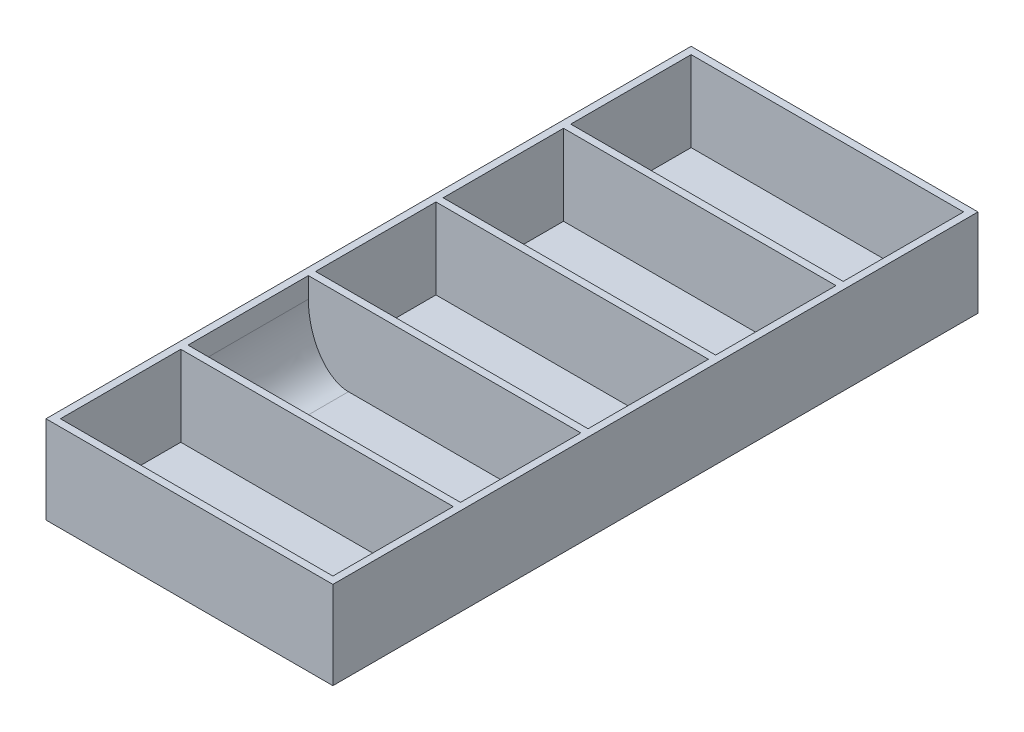
SolidWorks part; units mm, degrees
note: The reader was unsure of these and kept them because the rebuilt part matched: shared geometry of "Sketch1<6>".
ref_plane "Front Plane" through (0, 0, 0) normal (0, 0, 1) x (1, 0, 0)
ref_plane "Top Plane" through (0, 0, 0) normal (0, 1, 0) x (1, 0, 0)
ref_plane "Right Plane" through (0, 0, 0) normal (1, 0, 0) x (0, 0, -1)
sketch "Sketch1" plane through (0, 0, 0) normal (0, 1, 0) x (1, 0, 0)
  line L53 (0, 0) -> (71.6, 0)
  line L54 (0, 0) -> (0, 161)
  line L55 (0, 161) -> (71.6, 161)
  line L56 (71.6, 0) -> (71.6, 161)
  line L57 (1.8, 31.84) -> (69.8, 31.84)
  line L58 (1.8, 31.84) -> (1.8, 1.8)
  line L59 (1.8, 1.8) -> (69.8, 1.8)
  line L60 (69.8, 31.84) -> (69.8, 1.8)
  line L61 (1.8, 95.52) -> (69.8, 95.52)
  line L62 (1.8, 95.52) -> (1.8, 65.48)
  line L63 (1.8, 65.48) -> (69.8, 65.48)
  line L64 (69.8, 95.52) -> (69.8, 65.48)
  line L65 (69.8, 63.68) -> (1.8, 63.68)
  line L66 (69.8, 63.68) -> (69.8, 33.64)
  line L67 (69.8, 33.64) -> (1.8, 33.64)
  line L68 (1.8, 63.68) -> (1.8, 33.64)
  line L69 (69.8, 97.32) -> (1.8, 97.32)
  line L70 (69.8, 97.32) -> (69.8, 127.36)
  line L71 (69.8, 127.36) -> (1.8, 127.36)
  line L72 (1.8, 97.32) -> (1.8, 127.36)
  line L73 (69.8, 129.16) -> (1.8, 129.16)
  line L74 (69.8, 129.16) -> (69.8, 159.2)
  line L75 (69.8, 159.2) -> (1.8, 159.2)
  line L76 (1.8, 129.16) -> (1.8, 159.2)
  dimension "D1" = 71.6
  dimension "D2" = 161
  dimension "D3" = 1.8
  dimension "D4" = 1.8
  dimension "D5" = 1.8
  dimension "D6" = 1.8
  dimension "D9" = 1.8
  dimension "D7" = 1.8
  dimension "D8" = 1.8
  dimension "D10" = 1.8
extrude "Boss-Extrude1" add sketch "Sketch1" against normal blind 1.8 contours L60 L57 L58 L59 | L65 L68 L67 L66 | L64 L61 L62 L63 | L72 L69 L70 L71 | L76 L73 L74 L75 | L53 L56 L55 L54 L68 L65 L66 L67 L57 L60 L59 L58 L61 L64 L63 L62 L69 L72 L71 L70 L73 L76 L75 L74
extrude "Boss-Extrude2" add sketch "Sketch1<6>" along normal blind 20.1
sketch "Sketch1<6>" plane through (0, 0, 0) normal (0, 1, 0) x (1, 0, 0) same geometry as "Sketch1"
fillet "Fillet3" radius 10 2 edges at (69.8, 0, -144.18) (35.8, 0, -159.2)
fillet "Fillet4" radius 15 1 edges at (69.8, 0, -112.34)
fillet "Fillet5" radius 15 2 edges at (35.8, 0, -95.52) (69.8, 0, -80.5)
fillet "Fillet6" radius 10 2 edges at (35.8, 0, -33.64) (1.8, 0, -48.66)
fillet "Fillet7" radius 15 2 edges at (69.8, 0, -48.66)
equation "\"padding\"= 1.8"
equation "\"D3@Sketch1\"=\"padding\""
equation "\"D4@Sketch1\"=\"padding\""
equation "\"D5@Sketch1\"=\"padding\""
equation "\"D1@Boss-Extrude1\"=\"padding\""
equation "\"D6@Sketch1\"=\"padding\""
equation "\"D9@Sketch1\"=\"padding\""
equation "\"D7@Sketch1\"=\"padding\""
equation "\"D8@Sketch1\"=\"padding\""
equation "\"D10@Sketch1\"=\"padding\""
